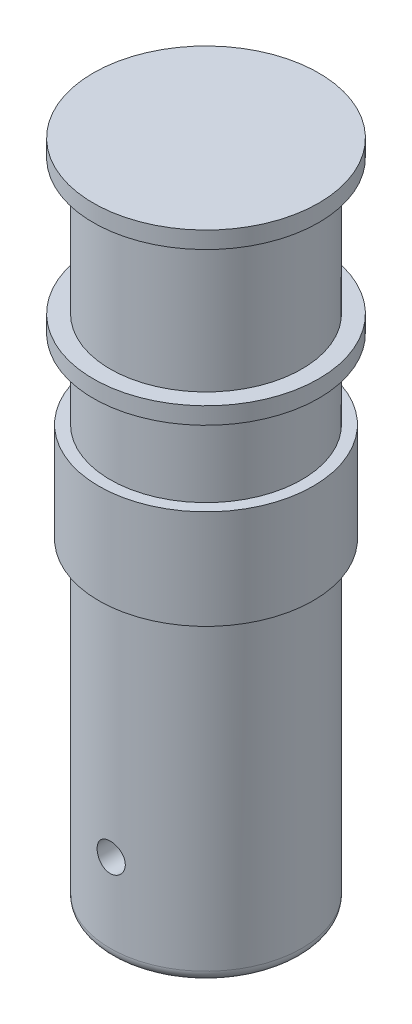
SolidWorks part; units mm, degrees
material "ABS"
ref_plane "Front Plane" through (0, 0, 0) normal (0, 0, 1) x (1, 0, 0)
ref_plane "Top Plane" through (0, 0, 0) normal (0, 1, 0) x (1, 0, 0)
ref_plane "Right Plane" through (0, 0, 0) normal (1, 0, 0) x (0, 0, -1)
sketch "Sketch1" plane through (0, 0, 0) normal (0, 0, 1) x (1, 0, 0)
  line L2 (-8.5, -44) -> (-8.5, -15.8)
  line L3 (-8.5, 0) -> (-10, 0)
  line L4 (-10, 0) -> (-10, 1.5)
  line L5 (-10, 1.5) -> (-8.5, 1.5)
  line L6 (-8.5, 1.5) -> (-8.5, 13.5)
  line L7 (-8.5, 13.5) -> (-10, 13.5)
  line L8 (-10, 13.5) -> (-10, 15)
  line L9 (-10, 15) -> (0, 15)
  line L10 (0, 15) -> (0, -30)
  line L11 (-4, -44) -> (-8.5, -44)
  line L12 (-4, -30) -> (-4, -44)
  line L13 (0, -30) -> (-4, -30)
  line L14 (-8.5, -15.8) -> (-9.5, -15.8)
  line L16 (-9.5, -15.8) -> (-9.5, -7)
  line L17 (-9.5, -7) -> (-8.5, -7)
  line L18 (-8.5, -7) -> (-8.5, 0)
  dimension "D1" = 8.5
  dimension "D2" = 1.5
  dimension "D3" = 44
  dimension "D4" = 1.5
  dimension "D5" = 4
  dimension "D6" = 14
  dimension "D7" = 15
  dimension "D8" = 10
  dimension "D9" = 28.2
  dimension "D10" = 1
  dimension "D11" = 7
revolve "Revolve1" add sketch "Sketch1" angle 360 about L10
fillet "Fillet1" radius 1 2 edges at (-8.5, -44, 0) (-4, -44, 0)
hole_wizard "M3x0.5 Tapped Hole1" positions "Sketch2" profile "Sketch3" tap size "M3x0.5" standard "ANSI Metric" end condition up to next
sketch "Sketch2" plane through (0, 0, 0) normal (0, 0, 1) x (1, 0, 0)
  line L0 (-7.5, -44) -> (7.5, -44) construction
  point P0 (0, -36)
  dimension "D1" = 8
sketch "Sketch3" plane through (0, -36, 0) normal (1, 0, 0) x (0, 1, 0)
  line L0 (0, 0) -> (0, 8.5)
  line L1 (0, 8.5) -> (1.25, 8.5)
  line L2 (1.25, 8.5) -> (1.25, 0)
  line L5 (1.25, 0) -> (0, 0)
  line L11 (0, -6.35) -> (0, 107.95) construction
  dimension "Thru Tap Drill Dia." = 2.5
  dimension "Thru Tap Drill Depth" = 8.5
cosmetic thread "Hole Thread1" parameters "D2"=3
